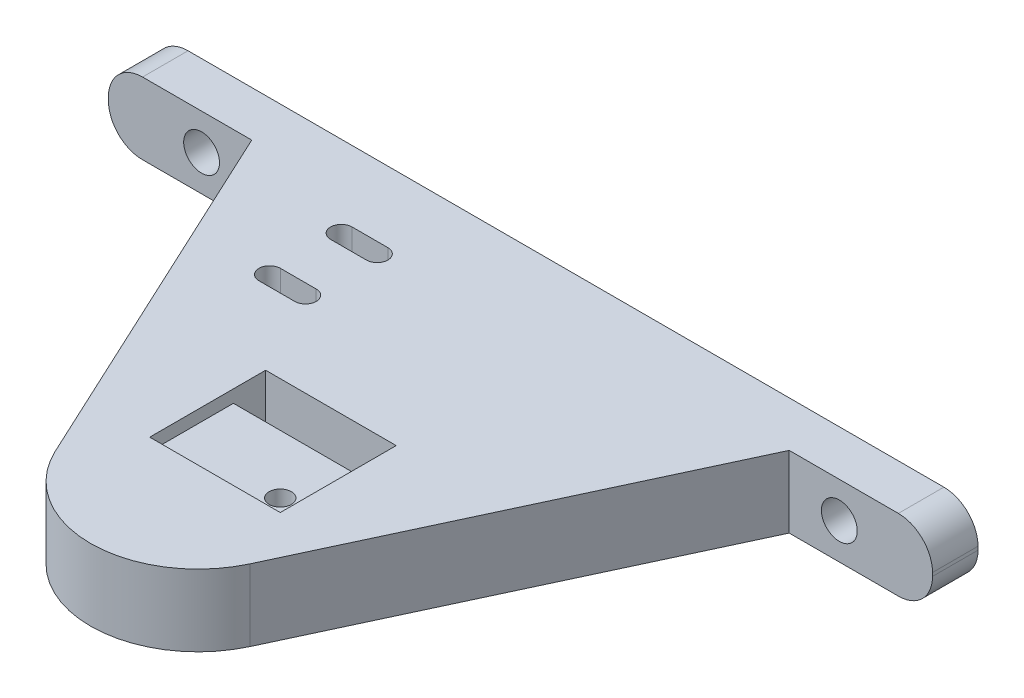
SolidWorks part; units mm, degrees
note: The reader was unsure of these and kept them because the rebuilt part matched: shared geometry of "Sketch8<9>".
ref_plane "Front Plane" through (0, 0, 0) normal (0, 0, 1) x (1, 0, 0)
ref_plane "Top Plane" through (0, 0, 0) normal (0, 1, 0) x (1, 0, 0)
ref_plane "Right Plane" through (0, 0, 0) normal (1, 0, 0) x (0, 0, -1)
sketch "Sketch1" plane through (0, 0, 0) normal (0, 0, 1) x (1, 0, 0)
  line L0 (-57.5, 0) -> (57.5, 0) construction
  line L1 (-57.5, -5) -> (57.5, -5)
  line L2 (-57.5, -5) -> (-57.5, 5)
  line L3 (-57.5, 5) -> (57.5, 5)
  line L4 (57.5, -5) -> (57.5, 5)
  line L5 (-57.5, -5) -> (57.5, 5) construction
  line L6 (-57.5, 5) -> (57.5, -5) construction
  circle A0 centre (44.5, 0) radius 2.075 construction
  circle A2 centre (44.5, 0) radius 2.5 construction
  point P0 (0, 0)
  point P8 (-44.5, 0)
  point P9 (44.5, 0)
  dimension "D5" = 4.15
  dimension "D6" = 5
  dimension "D1" = 89
  dimension "D2" = 44.5
  dimension "D3" = 115
  dimension "D4" = 10
extrude "Boss-Extrude1" add sketch "Sketch1" along normal blind 6.35 contours L1 L4 L3 L2
sketch "Sketch2" plane through (0, -5, 0) normal (0, -1, 0) x (1, 0, 0)
  line L2 (-57.5, 6.35) -> (57.5, 6.35) construction
  line L3 (57.5, 6.35) -> (57.5, 0)
  line L4 (57.5, 0) -> (-57.5, 0)
  line L5 (-57.5, 0) -> (-57.5, 6.35)
  line L6 (57.5, 6.35) -> (-57.5, 6.35)
  line L7 (-13.5981, 57.6818) -> (-37.5, 6.35)
  line L8 (13.5981, 57.6818) -> (37.5, 6.35)
  arc A0 (-13.5981, 57.6818) -> (13.5981, 57.6818) centre (0, 51.35) cw
  dimension "D1" = 15
  dimension "D2" = 45
  dimension "D3" = 20
  dimension "D4" = 20
extrude "Boss-Extrude3" add sketch "Sketch2" against normal up to surface (10 mm away) up to face at (0, 5, 3.175)
sketch "Sketch8" plane through (0, 5, 0) normal (0, 1, 0) x (-1, 0, 0)
  line L10 (-8.505, 34.195) -> (7.715, 34.195) construction
  line L11 (-8.505, 34.195) -> (-8.505, 48.375) construction
  line L12 (-8.505, 48.375) -> (7.715, 48.375) construction
  line L13 (7.715, 34.195) -> (7.715, 48.375) construction
  line L14 (-8.505, 34.195) -> (7.715, 48.375) construction
  line L15 (-8.505, 48.375) -> (7.715, 34.195) construction
  line L16 (-1.235, 42.725) -> (1.235, 42.725) construction
  line L17 (-1.235, 42.725) -> (-1.235, 47.275) construction
  line L18 (-1.235, 47.275) -> (1.235, 47.275) construction
  line L19 (1.235, 42.725) -> (1.235, 47.275) construction
  line L20 (-1.235, 42.725) -> (1.235, 47.275) construction
  line L21 (-1.235, 47.275) -> (1.235, 42.725) construction
  line L24 (-9.505, 33.195) -> (-9.505, 49.375)
  line L25 (-9.505, 49.375) -> (8.715, 49.375)
  line L26 (8.715, 49.375) -> (8.715, 33.195)
  line L27 (8.715, 33.195) -> (-9.505, 33.195)
  line L28 (-9.505, 37.695) -> (8.715, 37.695)
  point P0 (-6.4035, 51.2115)
  point P2 (-0.395, 41.285)
  point P13 (-2.1005, 31.2609)
  point P20 (-6.005, 45.875)
  point P22 (0, 45)
  dimension "D2" = 2.5
  dimension "D3" = 2.5
  dimension "D4" = 45
  dimension "D5" = 16.22
  dimension "D6" = 14.18
  dimension "D7" = 2.47
  dimension "D8" = 4.55
  dimension "D9" = 1.1
  dimension "D10" = 6.48
  dimension "D13" = 4.5
  dimension "D14" = 1
  dimension "D15" = 1
  dimension "D16" = 1
  dimension "D17" = 1
hole_wizard "M2.5 Clearance Hole1" positions "Sketch9" profile "Sketch10" hole size "M2.5" standard "ANSI Metric" end condition through all
sketch "Sketch9" plane through (0, 5, 0) normal (0, 1, 0) x (1, 0, 0)
  point P0 (6.005, -45.875)
sketch "Sketch10" plane through (6.005, 5, 45.875) normal (1, 0, 0) x (0, 0, 1)
  line L0 (0, 0) -> (0, 10)
  line L1 (0, 10) -> (1.55, 10)
  line L2 (1.55, 10) -> (1.55, 0)
  line L5 (1.55, 0) -> (0, 0)
  line L11 (0, -6.35) -> (0, 107.95) construction
  dimension "Thru Hole Dia." = 3.1
  dimension "Thru Hole Depth" = 10
extrude "Cut-Extrude3" cut sketch "Sketch8" against normal blind 1.75 contours L24 L28 L26 L25
extrude "Cut-Extrude4" cut sketch "Sketch8<9>" against normal through all contours L28 L24 L27 L26
sketch "Sketch8<9>" plane through (0, 5, 0) normal (0, 1, 0) x (-1, 0, 0) same geometry as "Sketch8"
fillet "Fillet2" radius 4.7625 4 edges at (57.5, 5, 3.175) (-57.5, 5, 3.175) (-57.5, -5, 3.175) (57.5, -5, 3.175)
hole_wizard "Ø5.0mm Dowel Hole1" positions "Sketch5" profile "Sketch7" hole size "Ø5.0" standard "KS" end condition through all
sketch "Sketch5" plane through (0, 0, 6.35) normal (0, 0, 1) x (1, 0, 0)
  point P0 (44.5, 0)
  point P3 (-44.5, 0)
sketch "Sketch7" plane through (44.5, 0, 6.35) normal (1, 0, 0) x (0, -1, 0)
  line L0 (0, 0) -> (0, 6.35)
  line L1 (0, 6.35) -> (2.5, 6.35)
  line L2 (2.5, 6.35) -> (2.5, 0)
  line L5 (2.5, 0) -> (0, 0)
  line L11 (0, -6.35) -> (0, 107.95) construction
  dimension "Thru Hole Dia." = 5
  dimension "Thru Hole Depth" = 6.35
sketch "Sketch11" plane through (0, 5, 0) normal (0, 1, 0) x (1, 0, 0)
  line L0 (-37.5, -6.35) -> (37.5, -6.35) construction
  line L1 (-20, -11.35) -> (-15, -11.35) construction
  line L2 (-20, -9.85) -> (-15, -9.85)
  line L3 (-20, -12.85) -> (-15, -12.85)
  line L4 (-20, -21.35) -> (-15, -21.35) construction
  line L5 (-20, -19.85) -> (-15, -19.85)
  line L6 (-20, -22.85) -> (-15, -22.85)
  line L7 (-17.5, -21.35) -> (-17.5, -11.35) construction
  arc A0 (-20, -9.85) -> (-20, -12.85) centre (-20, -11.35) ccw
  arc A1 (-15, -12.85) -> (-15, -9.85) centre (-15, -11.35) ccw
  arc A2 (-20, -19.85) -> (-20, -22.85) centre (-20, -21.35) ccw
  arc A3 (-15, -22.85) -> (-15, -19.85) centre (-15, -21.35) ccw
  point P6 (-17.5, -11.35)
  point P13 (-17.5, -21.35)
  dimension "D1" = 3
  dimension "D2" = 3
  dimension "D3" = 5
  dimension "D4" = 5
  dimension "D5" = 10
  dimension "D6" = 5
  dimension "D7" = 20
extrude "Cut-Extrude5" cut sketch "Sketch11" against normal through all
